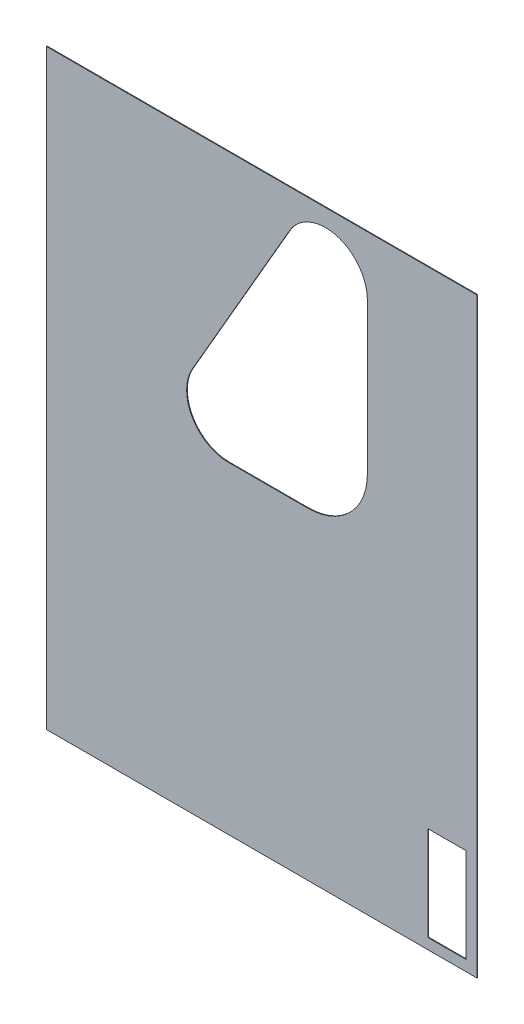
SolidWorks part; units mm, degrees
ref_plane "Front Plane" through (0, 0, 0) normal (0, 0, 1) x (1, 0, 0)
ref_plane "Top Plane" through (0, 0, 0) normal (0, 1, 0) x (1, 0, 0)
ref_plane "Right Plane" through (0, 0, 0) normal (1, 0, 0) x (0, 0, -1)
sketch "Sketch1" plane through (0, 0, 0) normal (0, 0, 1) x (1, 0, 0)
  line L1 (0, 0) -> (1215, 0)
  line L2 (0, 0) -> (0, 1670)
  line L3 (0, 1670) -> (1215, 1670)
  line L4 (1215, 0) -> (1215, 1670)
  line L5 (1185, 30) -> (1076.65, 30)
  line L6 (1185, 30) -> (1185, 296)
  line L7 (1185, 296) -> (1076.65, 296)
  line L8 (1076.65, 30) -> (1076.65, 296)
  dimension "D1" = 1215
  dimension "D2" = 1670
  dimension "D3" = 108.35
  dimension "D4" = 30
  dimension "D5" = 30
  dimension "D6" = 266
extrude "Boss-Extrude1" add sketch "Sketch1" along normal blind 2
extrude "Cut-Extrude1" cut sketch "Sketch2" against normal through all
sketch "Sketch2" plane through (-104.4366, -13.0714, 33) normal (0, 0, 1) x (1, 0, 0)
  line L0 (1010.4366, 1516.0714) -> (1010.4366, 1091.0714)
  line L1 (842.4366, 923.0714) -> (618.1953, 923.0714)
  line L2 (516.0043, 1100.0714) -> (790.2456, 1575.0714)
  arc A0 (1010.4366, 1091.0714) -> (842.4366, 923.0714) centre (842.4366, 1091.0714) cw
  arc A1 (618.1953, 923.0714) -> (516.0043, 1100.0714) centre (618.1953, 1041.0714) cw
  arc A2 (1010.4366, 1516.0714) -> (790.2456, 1575.0714) centre (892.4366, 1516.0714) ccw
  point P5 (799.5237, 866.5543)
  point P6 (321.2838, 682.0482)
  point P7 (955.4941, 1600.8385)
  point P12 (750.0994, 693.895)
